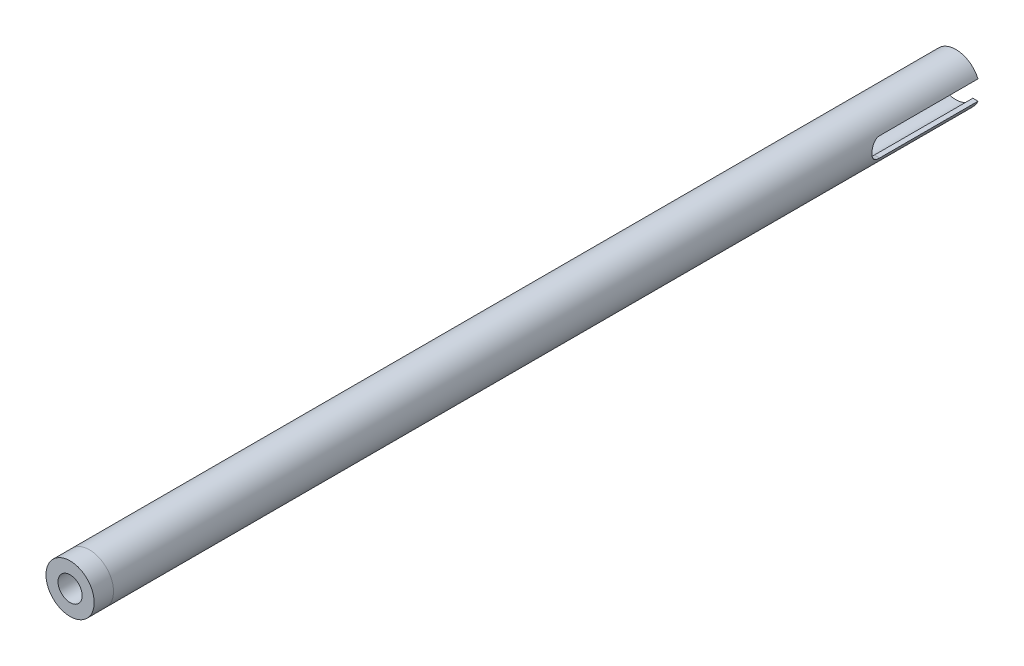
SolidWorks part; units mm, degrees
ref_plane "Front Plane" through (0, 0, 0) normal (0, 0, 1) x (1, 0, 0)
ref_plane "Top Plane" through (0, 0, 0) normal (0, 1, 0) x (1, 0, 0)
ref_plane "Right Plane" through (0, 0, 0) normal (1, 0, 0) x (0, 0, -1)
sketch "Axis" plane through (0, 0, 0) normal (0, 1, 0) x (1, 0, 0)
  line L0 (0, 0) -> (0, 291.4543) construction
  line L1 (0, 0) -> (0, -34.925) construction
  line L2 (0, 291.4543) -> (-7.9375, 291.4543) construction
  line L3 (0, 317.6601) -> (-28.3474, 224.0709) construction
  dimension "D1" = 34.925
  dimension "D2" = 7.9375
sketch "Sketch1" plane through (0, 0, 0) normal (0, 0, 1) x (1, 0, 0)
  line L0 (-7.9375, 0) -> (7.9375, 0) construction
  line L1 (-7.2748, 3.175) -> (7.2748, 3.175)
  line L2 (-7.2748, -3.175) -> (7.2748, -3.175)
  circle A0 centre (0, 0) radius 7.9375
  circle A1 centre (0, 0) radius 6.4135
  circle A2 centre (0, 0) radius 3.9688
  dimension "D1" = 15.875
  dimension "D3" = 7.9375
  dimension "D2" = 1.524
  dimension "D4" = 6.35
extrude "Threaded insert 1-1" add sketch "Sketch1" against normal blind 6.35 contours A2 L1 A1 | A1 L1 A0 | A2 L0 A1 L1 | A1 L0 A0 L1 | L0 A1 L2 A0 | L0 A2 L2 A1 | A2 L2 A1 | A1 L2 A0 | L0 A1 L2 A2 | L0 A0 L2 A1 | A0 L0 A1 L1 | A1 L0 A2 L1 region at (4.7887, 1.6543, 0) region at (4.7887, -1.6543, 0) region at (6.9234, 1.6163, 0) region at (6.9234, -1.6163, 0) region at (-4.7887, -1.6543, 0) region at (-4.7887, 1.6543, 0) region at (0, 4.6159, 0) region at (0, -4.6159, 0) region at (0, 6.5666, 0) region at (6.4237, -3.3281, 0) region at (-6.9234, -1.6163, 0) region at (-6.9234, 1.6163, 0)
extrude "Threaded insert 1-2" add sketch "Sketch1<3>" against normal blind 9.525 from surface contours A2 L1 A1 | A2 L0 A1 L1 | L0 A2 L2 A1 | A2 L2 A1 | L0 A1 L2 A2 | A1 L0 A2 L1 region at (4.7887, 1.6543, 0) region at (4.7887, -1.6543, 0) region at (-4.7887, -1.6543, 0) region at (-4.7887, 1.6543, 0) region at (0, 4.6159, 0) region at (0, -4.6159, 0) starting at face at (7.9375, 0, -6.35)
sketch "Sketch1<3>" plane through (0, 0, 0) normal (0, 0, 1) x (1, 0, 0) same geometry as "Sketch1"
extrude "A-arm tube" add sketch "Sketch1<4>" against normal up to vertex (291.4543 mm away) from surface separate body contours A1 L1 A0 | A1 L0 A0 L1 | L0 A1 L2 A0 | A1 L2 A0 | L0 A0 L2 A1 | A0 L0 A1 L1 region at (6.9234, 1.6163, 0) region at (6.9234, -1.6163, 0) region at (0, 6.5666, 0) region at (6.4237, -3.3281, 0) region at (-6.9234, -1.6163, 0) region at (-6.9234, 1.6163, 0) up to point (0, 0, -291.4543) starting at face at (6.4135, 0, -6.35)
sketch "Sketch1<4>" plane through (0, 0, 0) normal (0, 0, 1) x (1, 0, 0) same geometry as "Sketch1"
extrude "Apex slot" cut sketch "Sketch1<5>" along normal blind 35.56 from surface contours A0 L0 A1 L1 | L0 A0 L2 A1 | A1 L0 A0 L1 | L0 A1 L2 A0 region at (6.9234, 1.6163, 0) region at (6.9234, -1.6163, 0) region at (-6.9234, -1.6163, 0) region at (-6.9234, 1.6163, 0) starting at face at (6.4135, 0, -291.4543)
sketch "Sketch1<5>" plane through (0, 0, 0) normal (0, 0, 1) x (1, 0, 0) same geometry as "Sketch1"
fillet "Fillet1" radius 3.175 4 edges at (-6.4237, 3.175, -255.8943) (-6.4237, -3.175, -255.8943) (6.4237, -3.175, -255.8943) (6.4237, 3.175, -255.8943)
equation "\"tube diameter\"= 5 / 8"
equation "\"tube thickness\"= .06"
equation "\"apex thickness\"= .25"
equation "\"tube slot\"= 1.4"
equation "\"D1@Sketch1\"=\"tube diameter\""
equation "\"D2@Sketch1\"=\"tube thickness\""
equation "\"threaded insert hole\"= .3125"
equation "\"D3@Sketch1\"=\"threaded insert hole\""
equation "\"D4@Sketch1\"=\"apex thickness\""
equation "\"D1@Apex slot\" = \"tube slot\""
equation "\"D1@Fillet1\"=\"apex thickness\"/2"
equation "\"D2@Axis\"=\"tube diameter\"/2"
